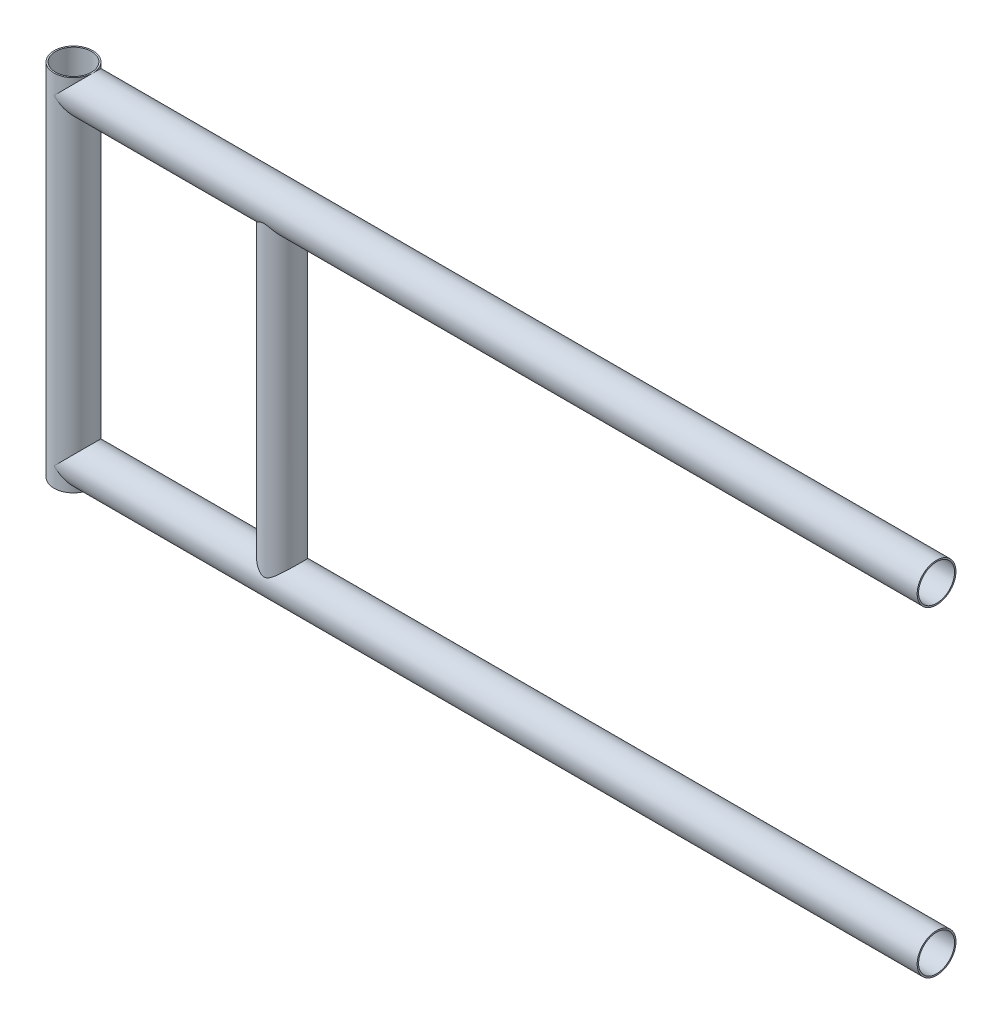
SolidWorks part; units mm, degrees
ref_plane "Front Plane" through (0, 0, 0) normal (0, 0, 1) x (1, 0, 0)
ref_plane "Top Plane" through (0, 0, 0) normal (0, 1, 0) x (1, 0, 0)
ref_plane "Right Plane" through (0, 0, 0) normal (1, 0, 0) x (0, 0, -1)
sketch "Sketch1" plane through (0, 0, 0) normal (0, 1, 0) x (1, 0, 0)
  circle A1 centre (0, 0) radius 13.5
  dimension "D2" = 27
extrude "Boss-Extrude3" add sketch "Sketch1" along normal mid plane 250
sketch "Sketch4" plane through (0, 0, 0) normal (1, 0, 0) x (0, 0, -1)
  line L0 (13.5, 0) -> (-13.5, 0) construction
  line L1 (13.5, -125) -> (13.5, 125) construction
  line L2 (-13.5, 125) -> (-13.5, -125) construction
  circle A2 centre (0, -111.5) radius 13.5
  circle A3 centre (0, 111.5) radius 13.5
  dimension "D1" = 27
extrude "Boss-Extrude4" add sketch "Sketch4" along normal blind 600
sketch "Sketch6" plane through (0, 0, 0) normal (0, 1, 0) x (1, 0, 0)
  circle A0 centre (145, 0) radius 12.5
  point P2 (0, 0)
  dimension "D1" = 25
  dimension "D2" = 145
extrude "Boss-Extrude5" add sketch "Sketch6" along normal mid plane 223
shell "Shell1" thickness 1 removed face at (600, -111.5, -13.5) removed face at (600, 111.5, 13.5) removed face at (0, 125, 13.5) removed face at (0, -125, 13.5)
